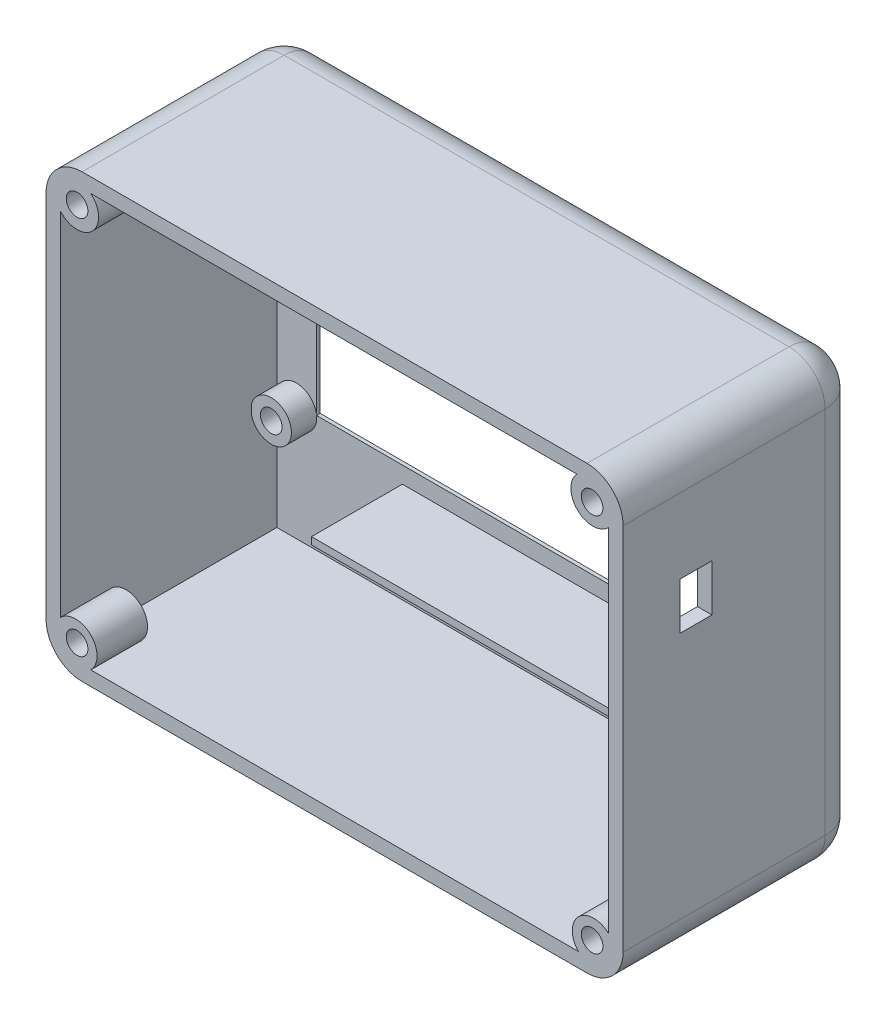
SolidWorks part; units mm, degrees
ref_plane "Plan de face" through (0, 0, 0) normal (0, 0, 1) x (1, 0, 0)
ref_plane "Plan de dessus" through (0, 0, 0) normal (0, 1, 0) x (1, 0, 0)
ref_plane "Plan de droite" through (0, 0, 0) normal (1, 0, 0) x (0, 0, -1)
sketch "Esquisse1" plane through (0, 0, 0) normal (0, 0, 1) x (1, 0, 0)
  line L5 (-21.4007, 19.2079) -> (41.2293, 19.2079)
  line L6 (-21.4007, 19.2079) -> (-21.4007, -19.7921)
  line L7 (-21.4007, -19.7921) -> (41.2293, -19.7921)
  line L8 (41.2293, 19.2079) -> (41.2293, -19.7921)
  line L11 (-26.9007, 21.2079) -> (-26.9007, -35.9921)
  line L14 (49.9993, 21.2079) -> (49.9993, -35.9921)
  line L16 (-26.9007, 21.2079) -> (49.9993, 21.2079)
  line L17 (-26.9007, -35.9921) -> (49.9993, -35.9921)
  circle A0 centre (-24.1859, 18.9079) radius 1.5
  circle A2 centre (43.8141, 18.9079) radius 1.5
  circle A4 centre (-24.1859, -20.0921) radius 1.5
  circle A5 centre (43.8141, -20.0921) radius 1.5
  dimension "D1" = 3
  dimension "D2" = 39
  dimension "D3" = 3
  dimension "D5" = 3
  dimension "D6" = 3
  dimension "D4" = 68
  dimension "D7" = 57.2
  dimension "D8" = 2
  dimension "D9" = 2.7852
  dimension "D10" = 39
  dimension "D11" = 68
  dimension "D12" = 76.9
  dimension "D13" = 5.5
  dimension "D14" = 62.63
  dimension "D15" = 39
extrude "Boss.-Extru.1" add sketch "Esquisse1" along normal blind 3
sketch "Esquisse2" plane through (0, 0, 0) normal (0, 0, 1) x (1, 0, 0)
  line L1 (45.5993, 21.2079) -> (49.0993, 21.2079)
  line L2 (45.5993, 21.2079) -> (45.5993, -22.0921)
  line L3 (45.5993, -22.0921) -> (49.0993, -22.0921)
  line L4 (49.0993, 21.2079) -> (49.0993, -22.0921)
extrude "Boss.-Extru.2" add sketch "Esquisse2" along normal blind 3
sketch "Esquisse3" plane through (0, 0, 0) normal (0, 0, 1) x (1, 0, 0)
  line L0 (-26.9007, -35.9921) -> (49.9993, -35.9921) construction
  line L1 (-26.9007, 21.2079) -> (49.0993, 21.2079)
  line L2 (-26.9007, 21.2079) -> (-26.9007, -35.9921)
  line L3 (-26.9007, -35.9921) -> (49.0993, -35.9921)
  line L4 (49.0993, 21.2079) -> (49.0993, -35.9921)
  line L5 (-28.9007, 23.2079) -> (51.0993, 23.2079)
  line L6 (-28.9007, 23.2079) -> (-28.9007, -37.9921)
  line L7 (-28.9007, -37.9921) -> (51.0993, -37.9921)
  line L8 (51.0993, 23.2079) -> (51.0993, -37.9921)
  line L10 (49.9993, 21.2079) -> (-26.9007, 21.2079) construction
  dimension "D1" = 2
  dimension "D2" = 2
  dimension "D3" = 2
  dimension "D4" = 2
  dimension "D5" = 0
  dimension "D6" = 0
extrude "Boss.-Extru.3" add sketch "Esquisse3" along normal blind 33
sketch "Esquisse4" plane through (0, 0, 3) normal (0, 0, 1) x (1, 0, 0)
  circle A0 centre (-24.1859, -20.0921) radius 1.5
  circle A1 centre (-24.1859, 18.9079) radius 1.5163
  circle A4 centre (-24.1859, 18.9079) radius 2.8013
  circle A7 centre (-24.1859, -20.0921) radius 2.8013
  circle A8 centre (43.8141, -20.0921) radius 1.5
  circle A9 centre (43.8141, -20.0921) radius 2.6021
  circle A10 centre (43.8141, 18.9079) radius 1.5
  circle A11 centre (43.8141, 18.9079) radius 2.6021
extrude "Boss.-Extru.4" add sketch "Esquisse4" along normal blind 3.5
sketch "Esquisse5" plane through (0, 0, 0) normal (0, 0, 1) x (1, 0, 0)
  circle A0 centre (-24.1859, 18.9079) radius 1.5
  circle A1 centre (-24.1859, -20.0921) radius 1.5
  circle A2 centre (43.8141, 18.9079) radius 1.5
  circle A3 centre (43.8141, -20.0921) radius 1.5
extrude "Boss.-Extru.5" add sketch "Esquisse5" along normal blind 2
fillet "Congé2" radius 5 4 edges at (-28.9007, -7.3921, 0) (11.0993, -37.9921, 0) (51.0993, -7.3921, 0) (11.0993, 23.2079, 0)
fillet "Congé3" radius 5 8 edges at (-27.4362, -36.5277, 1.4645) (49.6348, -36.5277, 1.4645) (49.6348, 21.7434, 1.4645) (-27.4362, 21.7434, 1.4645) (-28.9007, -37.9921, 19) (51.0993, -37.9921, 19) (51.0993, 23.2079, 19) (-28.9007, 23.2079, 19)
sketch "Esquisse6" plane through (49.0993, 0, 0) normal (-1, 0, 0) x (0, 0, 1)
  line L1 (20.7, 7.8579) -> (25.1418, 7.8579)
  line L2 (20.7, 7.8579) -> (20.7, 1.3579)
  line L3 (20.7, 1.3579) -> (25.1418, 1.3579)
  line L4 (25.1418, 7.8579) -> (25.1418, 1.3579)
  line L7 (33, 21.2079) -> (3, 21.2079) construction
  dimension "D2" = 13.35
  dimension "D3" = 6.5
extrude "Enlèv. mat.-Extru.1" cut sketch "Esquisse6" against normal blind 10
sketch "Esquisse8" plane through (0, 0, 33) normal (0, 0, 1) x (1, 0, 0)
  line L0 (49.0993, 21.2079) -> (45.031, 21.2079) construction
  line L1 (49.0993, -35.9921) -> (49.0993, 21.2079) construction
  line L4 (-26.9007, 21.2079) -> (-26.9007, 17.0079)
  line L5 (-26.9007, 21.2079) -> (-22.7007, 21.2079)
  line L11 (49.0993, 17.0079) -> (49.0993, 21.2079)
  line L12 (49.0993, 21.2079) -> (44.6967, 21.2079)
  line L13 (49.0993, 21.2079) -> (-26.9007, 21.2079) construction
  line L25 (-26.9007, -35.9921) -> (-22.7007, -35.9921)
  line L26 (-26.9007, -35.9921) -> (49.0993, -35.9921) construction
  line L27 (-26.9007, -35.9921) -> (-26.9007, -31.7921)
  line L28 (-26.9007, 21.2079) -> (-26.9007, -35.9921) construction
  line L29 (49.0993, -35.9921) -> (49.0993, -31.7921)
  line L30 (49.0993, -35.9921) -> (49.0993, 21.2079) construction
  line L31 (49.0993, -35.9921) -> (44.8993, -35.9921)
  circle A2 centre (46.7993, 18.9079) radius 1.5
  arc A4 (-26.9007, 17.0079) -> (-22.7007, 21.2079) centre (-24.6007, 18.9079) ccw
  arc A8 (44.6967, 21.2079) -> (49.0993, 17.0079) centre (46.898, 19.1079) ccw
  circle A17 centre (-24.6007, -33.6921) radius 1.5
  circle A18 centre (46.7993, -33.6921) radius 1.5
  arc A19 (-26.9007, -31.7921) -> (-22.7007, -35.9921) centre (-24.8007, -33.8921) cw
  arc A20 (44.8993, -35.9921) -> (49.0993, -31.7921) centre (47.0205, -33.9133) cw
  circle A21 centre (-24.6007, 18.9079) radius 1.5
  dimension "D3" = 3
  dimension "D6" = 2.3
  dimension "D5" = 4.2
  dimension "D8" = 3
  dimension "D9" = 3
  dimension "D10" = 3
  dimension "D16" = 2.3
  dimension "D19" = 0
  dimension "D18" = 2.97
  dimension "D1" = 2.3
  dimension "D2" = 2.3
  dimension "D4" = 4.2
  dimension "D7" = 2.3
  dimension "D11" = 71.4
  dimension "D12" = 4.2
  dimension "D13" = 2.3
  dimension "D14" = 2.3
  dimension "D15" = 4.2
  dimension "D17" = 71.4
extrude "Boss.-Extru.7" add sketch "Esquisse8" against normal blind 7
sketch "Esquisse9" plane through (0, -35.9921, 0) normal (0, 1, 0) x (1, 0, 0)
  line L0 (-22.7007, -33) -> (44.8993, -33) construction
  line L1 (31.1993, -22.4) -> (23.1993, -22.4)
  line L2 (31.1993, -22.4) -> (31.1993, -18.3)
  line L3 (31.1993, -18.3) -> (23.1993, -18.3)
  line L4 (23.1993, -22.4) -> (23.1993, -18.3)
  line L5 (49.0993, -26) -> (49.0993, -3) construction
  dimension "D1" = 10.6
  dimension "D2" = 4.1
  dimension "D3" = 17.9
  dimension "D4" = 8
chamfer "Chanfrein1" distance 2.5 angle 45 6 edges at (-21.4007, 18.7104, 0.0253) (41.2293, 18.7104, 0.0253) (-21.4007, -0.7921, 0) (9.9143, -19.7921, 0) (41.2293, -0.7921, 0) (9.9143, 19.2079, 0.101) first distance on face at (10.5068, 19.9674, 1.0101) first distance on face at (10.5068, -4.0921, 0)
sketch "Esquisse10" plane through (0, 0, 3) normal (0, 0, 1) x (1, 0, 0)
  line L1 (-9.5007, -22.0921) -> (49.0993, -22.0921)
  line L2 (-9.5007, -22.0921) -> (-9.5007, -23.0921)
  line L3 (-9.5007, -23.0921) -> (49.0993, -23.0921)
  line L4 (49.0993, -22.0921) -> (49.0993, -23.0921)
  line L5 (49.0993, -35.9921) -> (49.0993, 21.2079) construction
  line L6 (44.6967, 21.2079) -> (-22.7007, 21.2079) construction
  line L7 (-26.9007, 21.2079) -> (-26.9007, 19.599) construction
  dimension "D1" = 43.3
  dimension "D2" = 1
  dimension "D3" = 17.4
extrude "Boss.-Extru.8" add sketch "Esquisse10" along normal blind 12.6
